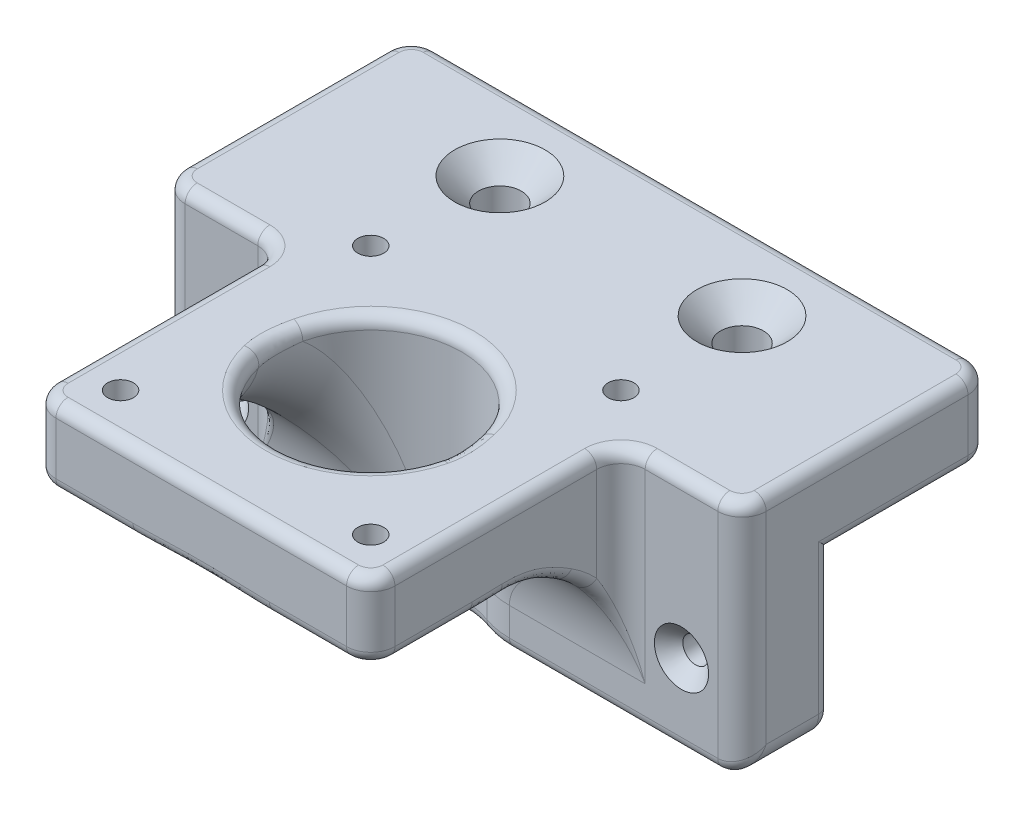
SolidWorks part; units mm, degrees
ref_plane "Front Plane" through (0, 0, 0) normal (0, 0, 1) x (1, 0, 0)
ref_plane "Top Plane" through (0, 0, 0) normal (0, 1, 0) x (1, 0, 0)
ref_plane "Right Plane" through (0, 0, 0) normal (1, 0, 0) x (0, 0, -1)
sketch "Sketch1" plane through (0, 0, 0) normal (0, 1, 0) x (1, 0, 0)
  line L1 (-15.5, 15.5) -> (15.5, 15.5) construction
  line L2 (-15.5, 15.5) -> (-15.5, -15.5) construction
  line L3 (-15.5, -15.5) -> (15.5, -15.5) construction
  line L4 (15.5, 15.5) -> (15.5, -15.5) construction
  line L5 (-21, 21) -> (21, 21)
  line L6 (-21, 21) -> (-21, -21)
  line L7 (-21, -21) -> (21, -21)
  line L8 (21, 21) -> (21, -21)
  line L9 (-21, -21) -> (-41, -21)
  line L10 (-21, -21) -> (-21, 41)
  line L11 (-21, 41) -> (-41, 41)
  line L12 (-41, -21) -> (-41, 41)
  line L13 (-21, 41) -> (21, 41)
  line L14 (-21, 41) -> (-21, 21)
  line L15 (-21, 21) -> (21, 21)
  line L16 (21, 41) -> (21, 21)
  circle A0 centre (0, 0) radius 11.25
  dimension "D1" = 22.5
  dimension "D2" = 15.5
  dimension "D3" = 15.5
  dimension "D4" = 31
  dimension "D5" = 31
  dimension "D6" = 42
  dimension "D7" = 42
  dimension "D8" = 21
  dimension "D9" = 21
  dimension "D10" = 20
  dimension "D11" = 20
extrude "Boss-Extrude1" add sketch "Sketch1" along normal blind 9.5 contours L8 L5 L6 L7 A0 | L14 L13 L16 L15 region at (0, 0, -20.406)
sketch "Sketch2" plane through (0, 0, 0) normal (0, 1, 0) x (1, 0, 0)
  point P0 (15.5, -15.5)
  point P2 (-15.5, -15.5)
  point P4 (15.5, 15.5)
  point P6 (-15.5, 15.5)
hole_wizard "CBORE for M3 SBHCS1" positions "Sketch2" profile "Sketch3" counterbore size "M3" standard "ANSI Metric" end condition through all
sketch "Sketch3" plane through (15.5, 0, 15.5) normal (1, 0, 0) x (0, 0, -1)
  line L0 (0, 0) -> (0, 9.5)
  line L1 (0, 9.5) -> (1.6, 9.5)
  line L3 (1.6, 9.5) -> (1.6, 1.65)
  line L4 (1.6, 1.65) -> (3.35, 1.65)
  line L5 (3.35, 1.65) -> (3.35, 0)
  line L7 (3.35, 0) -> (0, 0)
  line L11 (0, -6.35) -> (0, 107.95) construction
  dimension "Thru Hole Dia." = 3.2
  dimension "Thru Hole Depth" = 9.5
  dimension "C'Bore Dia." = 6.7
  dimension "C'Bore Depth" = 1.65
sketch "Sketch4" plane through (0, 9.5, 0) normal (0, 1, 0) x (1, 0, 0)
  line L0 (-31, 41) -> (-31, -21) construction
  line L1 (-21, 41) -> (-41, 41) construction
  line L2 (-21, -21) -> (-41, -21) construction
  line L3 (21, 31) -> (-41, 31) construction
  line L4 (21, 41) -> (21, 21) construction
  line L5 (-41, -21) -> (-41, 41) construction
  line L7 (-21, -21) -> (-21, 41) construction
  point P12 (15, 31)
  point P13 (-15, 31)
  point P14 (-31, 31)
  point P15 (-31, 10)
  point P16 (-31, -10)
  dimension "D1" = 6
  dimension "D2" = 11
  dimension "D3" = 6
hole_wizard "CSK for M5 SFHCS1" positions "Sketch4" profile "Sketch5" countersink size "M5" standard "ANSI Metric" end condition through all
sketch "Sketch5" plane through (-31, 9.5, 10) normal (1, 0, 0) x (0, 0, 1)
  line L0 (0, 0) -> (0, 9.5)
  line L1 (0, 9.5) -> (2.65, 9.5)
  line L2 (2.65, 9.5) -> (2.65, 2.95)
  line L3 (2.65, 2.95) -> (5.6, 0)
  line L5 (5.6, 0) -> (0, 0)
  line L6 (-2.65, 2.95) -> (-5.6, 0) construction
  line L11 (0, -6.35) -> (0, 107.95) construction
  dimension "Thru Hole Dia." = 5.3
  dimension "Thru Hole Depth" = 9.5
  dimension "Near C'Sink Dia." = 11.2
  dimension "Near C'Sink Angle" = 90
sketch "Sketch6" plane through (0, 0, 0) normal (0, -1, 0) x (1, 0, 0)
  line L0 (21, -21) -> (21, 21) construction
  line L1 (-21, -21) -> (21, -21)
  line L2 (-21, -21) -> (-21, -10)
  line L3 (-21, -10) -> (21, -10)
  line L4 (21, -21) -> (21, -10)
  dimension "D1" = 11
extrude "Boss-Extrude2" add sketch "Sketch6" along normal blind 20
sketch "Sketch13" plane through (0, 0, 0) normal (0, 1, 0) x (1, 0, 0)
  line L1 (-5.1539, 10) -> (5.1539, 10)
  line L2 (-5.1539, 10) -> (5.1539, 10)
  arc A1 (5.1539, 10) -> (-5.1539, 10) centre (0, 0) ccw
  arc A2 (5.1539, 10) -> (-5.1539, 10) centre (0, 0) ccw
  dimension "D1" = 0
extrude "Cut-Extrude2" cut sketch "Sketch13" against normal through all
fillet "Fillet7" radius 15 2 edges at (13.0769, 0, -10) (-13.0769, 0, -10)
chamfer "Chamfer1" [suppressed] distance 20 distance2 10
sketch "Sketch7" plane through (0, -20, 0) normal (0, -1, 0) x (1, 0, 0)
  circle A0 centre (15.5, -15.5) radius 3.35 construction
  circle A1 centre (-15.5, -15.5) radius 3.35 construction
  circle A2 centre (15.5, -15.5) radius 3.35
  circle A3 centre (-15.5, -15.5) radius 3.35
extrude "Cut-Extrude1" cut sketch "Sketch7" against normal blind 20
sketch "Sketch9" plane through (21, 0, 0) normal (1, 0, 0) x (0, 0, -1)
  line L0 (41, 9.5) -> (-21, 9.5) construction
  line L1 (21, -20) -> (10, -20)
  line L2 (21, -20) -> (21, 9.5)
  line L3 (21, 9.5) -> (10, 9.5)
  line L4 (10, -20) -> (10, 9.5)
  line L6 (41, 9.5) -> (21, 9.5)
  line L7 (41, 9.5) -> (41, 0)
  line L8 (41, 0) -> (21, 0)
  line L9 (21, 9.5) -> (21, 0)
  line M2 (21, 0) -> (41, 0)
  line M3 (41, 0) -> (41, 9.5)
  line M4 (41, 9.5) -> (-21, 9.5)
  line M8 (10, -20) -> (21, -20)
  line M9 (21, -20) -> (21, 0)
  dimension "D1" = 11
extrude "Boss-Extrude3" add sketch "Sketch9" along normal blind 15 contours L2 M2 M3 M4 | L4 L2 M8 M9 M4 region at (21, -5.25, -15.5) region at (21, 4.75, -31)
sketch "Sketch10" plane through (-21, 0, 0) normal (-1, 0, 0) x (0, 0, 1)
  line L0 (-41, 9.5) -> (21, 9.5) construction
  line L1 (-21, -20) -> (-10, -20)
  line L2 (-21, -20) -> (-21, 9.5)
  line L3 (-21, 9.5) -> (-10, 9.5)
  line L4 (-10, -20) -> (-10, 9.5)
  line L6 (-41, 9.5) -> (-21, 9.5)
  line L7 (-41, 9.5) -> (-41, 0)
  line L8 (-41, 0) -> (-21, 0)
  line L9 (-21, 9.5) -> (-21, 0)
  line M2 (-41, 0) -> (-21, 0)
  line M3 (-21, 0) -> (-21, -20)
  line M4 (-21, -20) -> (-10, -20)
  line M8 (21, 9.5) -> (-41, 9.5)
  line M9 (-41, 9.5) -> (-41, 0)
  dimension "D1" = 11
extrude "Boss-Extrude4" add sketch "Sketch10" along normal blind 15 contours L4 L2 M4 M8 M3 | L2 M2 M8 M9 region at (-21, -5.25, -15.5) region at (-21, 4.75, -31)
sketch "Sketch11" plane through (0, 0, -10) normal (0, 0, 1) x (1, 0, 0)
  line L0 (-21, 0) -> (21, 0) construction
  line L1 (-36, -20) -> (-21, -20) construction
  line L2 (-36, -20) -> (-36, 0) construction
  line L3 (-36, 0) -> (-21, 0) construction
  line L4 (-21, -20) -> (-21, 0) construction
  line L5 (21, 0) -> (36, 0) construction
  line L6 (21, 0) -> (21, -20) construction
  line L7 (21, -20) -> (36, -20) construction
  line L8 (36, 0) -> (36, -20) construction
  point P6 (-28.5, -10)
  point P14 (28.5, -10)
  point P15 (29.1321, -10)
  point P16 (0, 0)
  dimension "D1" = 7.5
  dimension "D2" = 7.5
hole_wizard "CSK for M3 SFHCS2" positions "Sketch11" profile "Sketch12" countersink size "M3" standard "ANSI Metric" end condition through all
sketch "Sketch12" plane through (28.5, -10, -10) normal (1, 0, 0) x (0, -1, 0)
  line L0 (0, 0) -> (0, 31)
  line L1 (0, 31) -> (1.6, 31)
  line L2 (1.6, 31) -> (1.6, 1.76)
  line L3 (1.6, 1.76) -> (3.36, 0)
  line L5 (3.36, 0) -> (0, 0)
  line L6 (-1.6, 1.76) -> (-3.36, 0) construction
  line L11 (0, -6.35) -> (0, 107.95) construction
  dimension "Thru Hole Dia." = 3.2
  dimension "Thru Hole Depth" = 31
  dimension "Near C'Sink Dia." = 6.72
  dimension "Near C'Sink Angle" = 90
fillet "Fillet5" radius 10 4 edges at (0, 0, 11.25) (-10.6195, -2.7902, -3.7133) (9.5643, -4.72, -5.9234) (5.1539, -17.5, -10)
fillet "Fillet4" radius 3 10 edges at (21, -2.75, -10) (-21, -2.75, -10) (36, 4.75, -41) (36, -5.25, -10) (21, 4.75, 21) (-21, 4.75, 21) (-36, -5.25, -10) (-36, 4.75, -41) (36, -20, -15.5) (-36, -20, -15.5)
fillet "Fillet2" radius 1.5 9 edges at (0, 9.5, -11.25) (0, -20, -11.25) (-35.1213, -19.1213, -10.8787) (-20.0904, -20, -10) (5.4657, -20, -10.1482) (-5.4657, -20, -10.1482) (0, 9.5, 11.2625)
fillet "Fillet6" radius 1.5 41 edges at (-36, -8.5, -21) (-35.1213, -19.1213, -21) (0, -20, -21) (35.1213, -19.1213, -21) (-35.1213, 0, -40.1213) (0, 0, -41) (35.1213, 0, -40.1213) (21.8787, 9.5, -9.1213) (28.5, 9.5, -10) (35.1213, 9.5, -10.8787) (36, 9.5, -25.5) (35.1213, 9.5, -40.1213) (0, 9.5, -41) (-35.1213, 9.5, -40.1213) (-36, 9.5, -25.5) (-35.1213, 9.5, -10.8787) (-28.5, 9.5, -10) (-21.8787, 9.5, -9.1213) (-21, 9.5, 5.5) (-20.1213, 9.5, 20.1213) (0, 9.5, 21) (20.1213, 9.5, 20.1213) (36, -8.5, -21) (21, 9.5, 5.5) (-36, 0, -29.5) (36, 0, -29.5) (-21, 0, 11.5) (-20.1213, 0, 20.1213) (21, 0, 11.5) (20.1213, 0, 20.1213) (10.625, 0, 21) (-10.625, 0, 21) (-21.3779, -8.3749, -8.4576) (-21, -2.8955, -3.859) (-21, -0.0092, 4.4747) (21.3779, -8.3749, -8.4576) (21, -0.0092, 4.4747) (21, -2.8955, -3.859) (0, 0.0031, 21)
